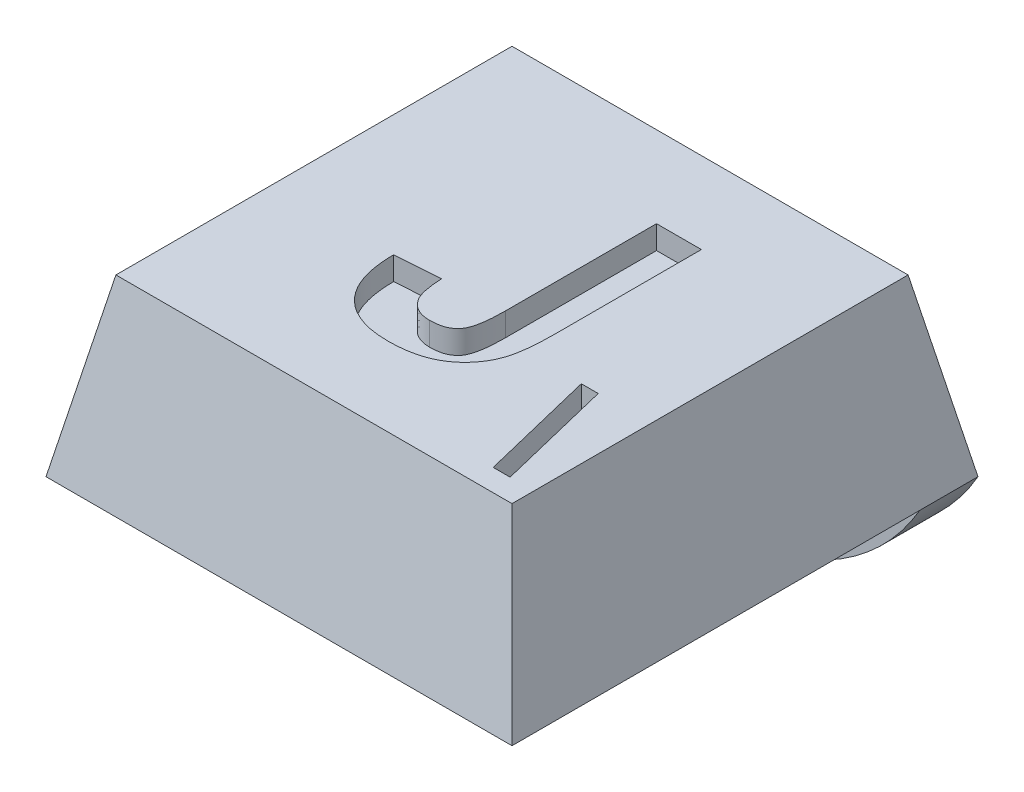
SolidWorks part; units mm, degrees
ref_plane "Front Plane" through (0, 0, 0) normal (0, 0, 1) x (1, 0, 0)
ref_plane "Top Plane" through (0, 0, 0) normal (0, 1, 0) x (1, 0, 0)
ref_plane "Right Plane" through (0, 0, 0) normal (1, 0, 0) x (0, 0, -1)
sketch "Sketch1" plane through (0, 0, 0) normal (0, 1, 0) x (1, 0, 0)
  line L1 (0, 0) -> (8, 0)
  line L2 (0, 0) -> (0, 8)
  line L3 (0, 8) -> (8, 8)
  line L4 (8, 0) -> (8, 8)
  dimension "D1" = 8
  dimension "D2" = 8
extrude "Boss-Extrude1" add sketch "Sketch1" along normal blind 3
sketch "Sketch2" plane through (0, 0, 0) normal (0, 0, 1) x (1, 0, 0)
  line L0 (0, 0) -> (0.6, 3)
  line L1 (0, 3) -> (8, 3) construction
  line L2 (0.6, 3) -> (0, 3)
  line L3 (0, 3) -> (0, 0)
  line L4 (8, 0) -> (7.4, 3)
  line L5 (7.4, 3) -> (8, 3)
  line L6 (8, 3) -> (8, 0)
  dimension "D1" = 0.6
  dimension "D2" = 0.6
extrude "Cut-Extrude1" cut sketch "Sketch2" against normal through all both and the other way through all
sketch "Sketch3" plane through (0, 0, 0) normal (1, 0, 0) x (0, 0, -1)
  line L0 (0, 0) -> (0.6, 3)
  line L1 (8, 3) -> (0, 3) construction
  line L2 (0.6, 3) -> (0, 3)
  line L3 (0, 3) -> (0, 0)
  line L4 (8, 3) -> (7.4, 3)
  line L5 (7.4, 3) -> (8, 0)
  line L6 (8, 3) -> (8, 0)
  dimension "D1" = 0.6
  dimension "D2" = 0.6
extrude "Cut-Extrude2" cut sketch "Sketch3" along normal blind 11
sketch "Sketch4" plane through (0, 0, 0) normal (0, -1, 0) x (1, 0, 0)
  line L0 (8, 0) -> (8, -8) construction
  line L3 (0, 0) -> (8, 0) construction
  circle A0 centre (4, -3.75) radius 1.75
  dimension "D1" = 3.5
  dimension "D2" = 4
  dimension "D3" = 3.75
extrude "Cut-Extrude3" cut sketch "Sketch4" against normal blind 0.4
sketch "Sketch5" plane through (0, 0, 0) normal (0, -1, 0) x (1, 0, 0)
  line L0 (8, 0) -> (8, -8) construction
  line L1 (0, -8) -> (8, -8)
  line L2 (0, -8) -> (0, -7)
  line L3 (0, -7) -> (8, -7)
  line L4 (8, -8) -> (8, -7)
  dimension "D1" = 1
extrude "Boss-Extrude2" add sketch "Sketch5" along normal blind 2
fillet "Fillet1" radius 4 2 edges at (8, -2, -7.5) (0, -2, -7.5)
sketch "Sketch6" plane through (0, 3, 0) normal (0, 1, 0) x (1, 0, 0)
  text T0 "J" font "Arial" height 4
extrude "Cut-Extrude4" cut sketch "Sketch6" against normal blind 0.4
sketch "Sketch7" plane through (0, 3, 0) normal (0, 1, 0) x (1, 0, 0)
  text T0 "\\" font "Arial" height 2
extrude "Cut-Extrude5" cut sketch "Sketch7" against normal blind 0.5
